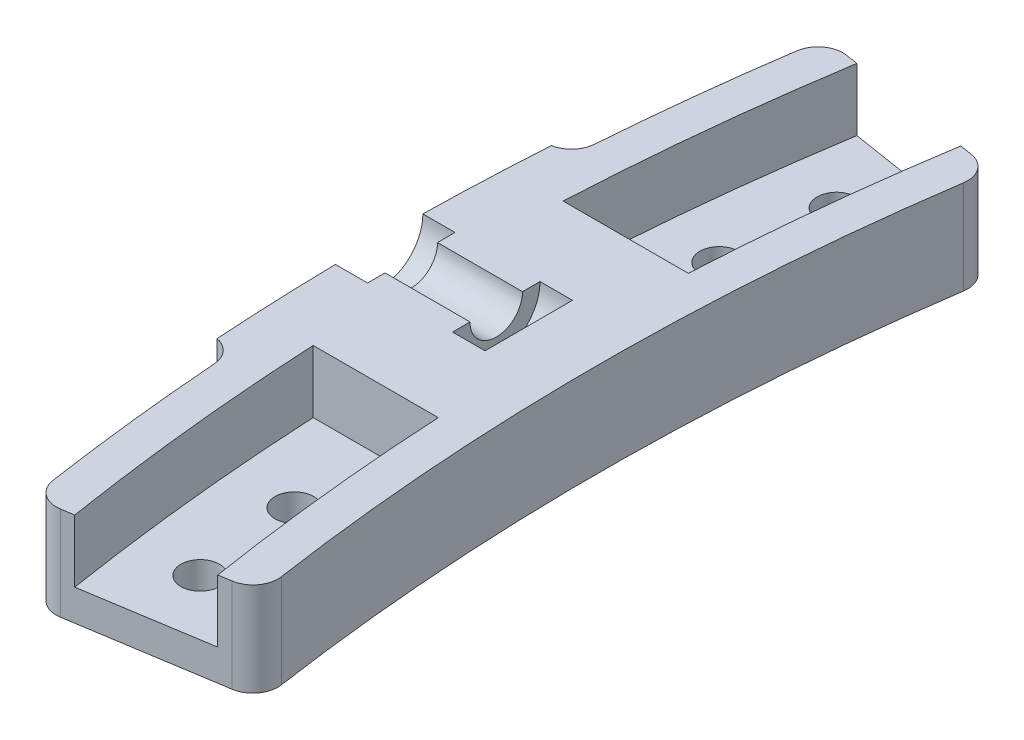
SolidWorks part; units mm, degrees
ref_plane "Front Plane" through (0, 0, 0) normal (0, 0, 1) x (1, 0, 0)
ref_plane "Top Plane" through (0, 0, 0) normal (0, 1, 0) x (1, 0, 0)
ref_plane "Right Plane" through (0, 0, 0) normal (1, 0, 0) x (0, 0, -1)
sketch "Sketch1" plane through (0, 0, 0) normal (0, 1, 0) x (1, 0, 0)
  line L0 (0, 0) -> (-197.5377, -31.2869) construction
  line L1 (0, 0) -> (-197.5377, 31.2869) construction
  line L2 (0, 0) -> (-195, 0) construction
  line L3 (-197.5377, 31.2869) -> (-187.6608, 29.7225)
  line L4 (-187.6608, -29.7225) -> (-197.5377, -31.2869)
  line L5 (0, 0) -> (-200.5007, -31.7562) construction
  line L6 (0, 0) -> (-200.5007, 31.7562) construction
  line L7 (-200.5007, 31.7562) -> (-184.6977, 29.2532)
  line L8 (-200.5007, -31.7562) -> (-184.6977, -29.2532)
  arc A0 (-197.5377, 31.2869) -> (-197.5377, -31.2869) centre (0, 0) ccw
  arc A1 (-187.6608, 29.7225) -> (-187.6608, -29.7225) centre (0, 0) ccw
  arc A2 (-192.5992, -30.5047) -> (-192.5992, 30.5047) centre (0, 0) cw construction
  arc A4 (-184.6977, 29.2532) -> (-184.6977, -29.2532) centre (0, 0) ccw
  arc A5 (-200.5007, 31.7562) -> (-200.5007, -31.7562) centre (0, 0) ccw
  dimension "D1" = 200
  dimension "D2" = 190
  dimension "D3" = 5
  dimension "D5" = 187
  dimension "D6" = 203
  dimension "D4" = 18
extrude "Boss-Extrude1" add sketch "Sketch1" along normal blind 7.5 contours A1 L3 A0 L4 | L7 A5 L8 A0 | A4 L7 A1 L8 region at (-200.6761, 0, 0) region at (-194.2416, 0, 0) region at (-187.7297, 0, 0)
ref_plane "Plane1" through (-195, 0, 0) normal (1, 0, 0) x (0, 0, -1)
sketch "Sketch19" plane through (0, 0, 0) normal (0, 1, 0) x (1, 0, 0)
  line L0 (0, 0) -> (-204.0621, 13.3749) construction
  line L1 (0, 0) -> (-204.0621, -13.3749) construction
  line L4 (0, 0) -> (-204.5, 0) construction
  line L5 (-204.0621, 13.3749) -> (-202.5654, 13.2768)
  line L6 (-204.0621, -13.3749) -> (-202.5654, -13.2768)
  arc A0 (-204.0621, 13.3749) -> (-204.0621, -13.3749) centre (0, 0) ccw
  arc A1 (-200.5007, 31.7562) -> (-200.5007, -31.7562) centre (0, 0) ccw construction
  arc A2 (-202.5654, 13.2768) -> (-202.5654, -13.2768) centre (0, 0) ccw
  dimension "D1" = 204.5
  dimension "D2" = 3.75
extrude "Boss-Extrude2" add sketch "Sketch19" along normal blind 7.5
sketch "Sketch15" plane through (0, 7.5, 0) normal (0, 1, 0) x (1, 0, 0)
  line L0 (-187.6608, -29.7225) -> (-197.5377, -31.2869) construction
  line L1 (-185, 10) -> (-205, 10)
  line L2 (-185, 10) -> (-185, -10)
  line L3 (-185, -10) -> (-205, -10)
  line L4 (-205, 10) -> (-205, -10)
  line L5 (-185, 10) -> (-205, -10) construction
  line L6 (-185, -10) -> (-205, 10) construction
  line L7 (-197.5377, 31.2869) -> (-187.6608, 29.7225) construction
  line L8 (-187.6608, -29.7225) -> (-197.5377, -31.2869)
  line L9 (-197.5377, 31.2869) -> (-187.6608, 29.7225)
  arc A2 (-187.6608, 29.7225) -> (-187.6608, -29.7225) centre (0, 0) ccw construction
  arc A3 (-197.5377, 31.2869) -> (-197.5377, -31.2869) centre (0, 0) ccw construction
  arc A4 (-187.6608, 29.7225) -> (-187.6608, -29.7225) centre (0, 0) ccw
  arc A5 (-197.5377, 31.2869) -> (-197.5377, -31.2869) centre (0, 0) ccw
  point P0 (-195, 0)
  line M5 (-200.5007, -31.7562) -> (-184.6977, -29.2532)
  line M7 (-184.6977, 29.2532) -> (-200.5007, 31.7562)
  dimension "D1" = 20
  dimension "D2" = 20
extrude "Cut-Extrude1" cut sketch "Sketch15" against normal blind 5 contours A5 L1 A4 M7 | L3 A5 A4 M5 region at (-193.9153, 7.5, -20.2762) region at (-193.9153, 7.5, 20.2762)
ref_plane "Plane2" through (-195, 0, 0) normal (-1, 0, 0) x (0, 0, 1)
sketch "Sketch12" plane through (0, 0, 0) normal (0, 1, 0) x (1, 0, 0)
  line L0 (0, 0) -> (-194.258, -16.9954) construction
  line L1 (0, 0) -> (-193.3317, -25.4526) construction
  line L2 (0, 0) -> (-195, 0) construction
  line L3 (0, 0) -> (-195, 0) construction
  line L4 (0, 0) -> (-194.258, 16.9954) construction
  line L5 (0, 0) -> (-193.3317, 25.4526) construction
  arc A0 (-192.5992, 30.5047) -> (-192.5992, -30.5047) centre (0, 0) ccw construction
  dimension "D1" = 10
  dimension "D2" = 15
hole_wizard "Ø3.1 (3.1) Diameter Hole2" positions "Sketch18" profile "Sketch17" hole size "Ø3.1" standard "ISO" end condition through all
sketch "Sketch18" plane through (0, 0, 0) normal (0, -1, 0) x (-1, 0, 0)
  point P0 (193.3317, -25.4526)
  point P3 (194.258, -16.9954)
  point P6 (194.258, 16.9954)
  point P9 (193.3317, 25.4526)
sketch "Sketch17" plane through (-193.3317, 0, 25.4526) normal (1, 0, 0) x (0, 0, -1)
  line L0 (0, 0) -> (0, 7.5)
  line L1 (0, 7.5) -> (1.55, 7.5)
  line L2 (1.55, 7.5) -> (1.55, 0)
  line L5 (1.55, 0) -> (0, 0)
  line L11 (0, -6.35) -> (0, 107.95) construction
  dimension "Thru Hole Dia." = 3.1
  dimension "Thru Hole Depth" = 7.5
sketch "Sketch20" plane through (0, 0, 0) normal (0, 1, 0) x (1, 0, 0)
  line L0 (-205, 0) -> (-192.5, 0) construction
  line L1 (0, 0) -> (-205, 0) construction
  arc A2 (-204.0621, 13.3749) -> (-204.0621, -13.3749) centre (0, 0) ccw construction
  point P3 (-204.5, 0)
  dimension "D1" = 205
  dimension "D2" = 12.5
ref_plane "Plane3" through (-192.5, 0, 0) normal (1, 0, 0) x (0, 0, -1)
sketch "Sketch21" plane through (-192.5, 0, 0) normal (1, 0, 0) x (0, 0, -1)
  line L0 (29.2532, 7.5) -> (-29.2532, 7.5) construction
  circle A0 centre (0, 7.5) radius 3.5
  dimension "D1" = 7
extrude "Cut-Extrude2" cut sketch "Sketch21" against normal blind 2.6
sketch "Sketch22" plane through (-195.1, 0, 0) normal (1, 0, 0) x (0, 0, -1)
  line L0 (29.2532, 7.5) -> (-29.2532, 7.5) construction
  circle A0 centre (0, 7.5) radius 2.1
  dimension "D1" = 4.2
ref_plane "Plane4" through (-204.5, 0, 0) normal (1, 0, 0) x (0, 0, -1)
sketch "Sketch23" plane through (-204.5, 0, 0) normal (1, 0, 0) x (0, 0, -1)
  circle A0 centre (0, 7.5) radius 3.5
  dimension "D1" = 7
extrude "Cut-Extrude3" cut sketch "Sketch23" along normal blind 2.6
extrude "Cut-Extrude4" cut sketch "Sketch22" against normal through all contours A0
fillet "Fillet1" radius 2 4 edges at (-200.5007, 3.75, -31.7562) (-184.6977, 3.75, -29.2532) (-184.6977, 3.75, 29.2532) (-200.5007, 3.75, 31.7562)
fillet "Fillet2" radius 2 2 edges at (-202.5654, 3.75, -13.2768) (-202.5654, 3.75, 13.2768)
